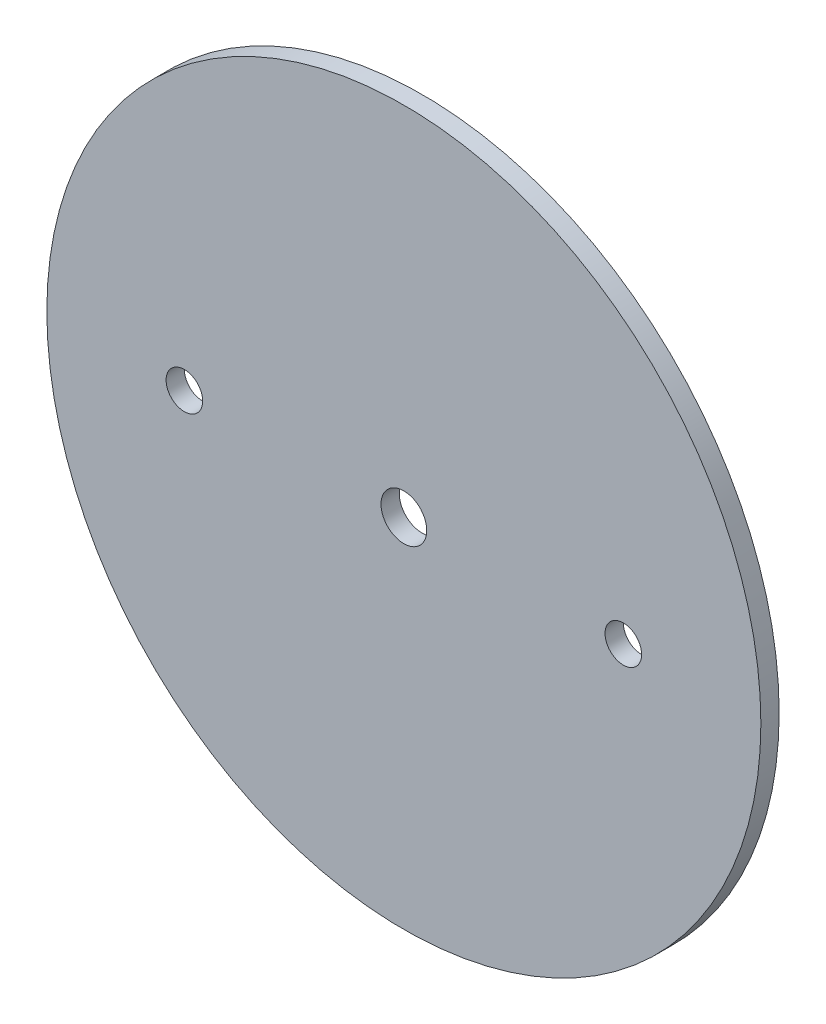
SolidWorks part; units mm, degrees
ref_plane "Front Plane" through (0, 0, 0) normal (0, 0, 1) x (1, 0, 0)
ref_plane "Top Plane" through (0, 0, 0) normal (0, 1, 0) x (1, 0, 0)
ref_plane "Right Plane" through (0, 0, 0) normal (1, 0, 0) x (0, 0, -1)
sketch "Sketch1" plane through (0, 0, 0) normal (0, 0, 1) x (1, 0, 0)
  circle A0 centre (0, 0) radius 61.976
  dimension "D1" = 123.952
extrude "Boss-Extrude1" add sketch "Sketch1" along normal mid plane 3.175
sketch "Sketch2" plane through (0, 0, 1.5875) normal (0, 0, 1) x (1, 0, 0)
  line L0 (-1000, 0) -> (49000, 0) construction
  line L1 (0, -1000) -> (0, 49000) construction
  point P4 (38.1, 0)
  point P5 (-38.1, 0)
  dimension "D2" = 76.2
  dimension "D1" = 38.1
hole_wizard "1/4 (0.25) Diameter Hole1" positions "Sketch2" profile "Sketch3" hole size "1/4" standard "ANSI Inch" end condition through all
sketch "Sketch3" plane through (-38.1, 0, 1.5875) normal (1, 0, 0) x (0, -1, 0)
  line L0 (0, 0) -> (0, 3.175)
  line L1 (0, 3.175) -> (3.175, 3.175)
  line L2 (3.175, 3.175) -> (3.175, 0)
  line L5 (3.175, 0) -> (0, 0)
  line L11 (0, -6.35) -> (0, 107.95) construction
  dimension "Thru Hole Dia." = 6.35
  dimension "Thru Hole Depth" = 3.175
sketch "Sketch4" plane through (0, 0, 1.5875) normal (0, 0, 1) x (1, 0, 0)
  point P0 (0, 0)
hole_wizard "5/16 (0.3125) Diameter Hole1" positions "Sketch4" profile "Sketch5" hole size "5/16" standard "ANSI Inch"
sketch "Sketch5" plane through (0, 0, 1.5875) normal (1, 0, 0) x (0, -1, 0)
  line L0 (0, 0) -> (0, 3.302)
  line L1 (0, 3.302) -> (3.9687, 3.302)
  line L2 (3.9687, 3.302) -> (3.9688, 0)
  line L5 (3.9688, 0) -> (0, 0)
  line L10 (0, 3.302) -> (-3.9688, 3.302) construction
  line L11 (0, -6.35) -> (0, 107.95) construction
  dimension "Hole Dia." = 7.9375
  dimension "Hole Depth" = 3.302
  dimension "Drill Angle" = 180
equation "\"AIRFRAME_OD\"= 5.15in"
equation "\"AIRFRAME_ID\"= 5.00in"
equation "\"FLAT_T\"= 0.125in"
equation "\"NOSE_EXP_L\"= 27in"
equation "\"NOSE_SHOULDER_L\"= 5in"
equation "\"MAIN_L\"= 30in"
equation "\"RECO_COUP_L\"= 10in"
equation "\"RECO_SWITCH_L\"= 2in"
equation "\"DROGUE_L\"= 20in"
equation "\"ATS_FORE_COUP_L\"= 5.5in"
equation "\"ATS_AFT_COUP_L\"= 4.5in"
equation "\"LOWER_L\"= 30in"
equation "\"FIN_N\"= 4"
equation "\"CR_AFT_X\"= 0.5in"
equation "\"CR_FORE_X\"= 9.25in"
equation "\"FIN_ROOT\"= 8in"
equation "\"FIN_X\"= 0.75in"
equation "\"MOTOR_OD\"= 3.091in"
equation "\"MOTOR_ID\"= 3.00in"
equation "\"COUPLER_OD\"= 4.998in"
equation "\"COUPLER_ID\"= 4.88in"
equation "\"D1@Sketch1\"=\"COUPLER_ID\""
equation "\"D1@Boss-Extrude1\"=\"FLAT_T\""
equation "\"RECO_ROD_X\"= 3.5in"
equation "\"ATS_ROD_X\"= 3in"
equation "\"D2@Sketch2\"=\"ATS_ROD_X\""
equation "\"MOTOR_L\"= 14in"
equation "\"MOTOR_LOWER_X\"= 2in"
equation "\"D1@Sketch2\"=\"ATS_ROD_X\"/2"
